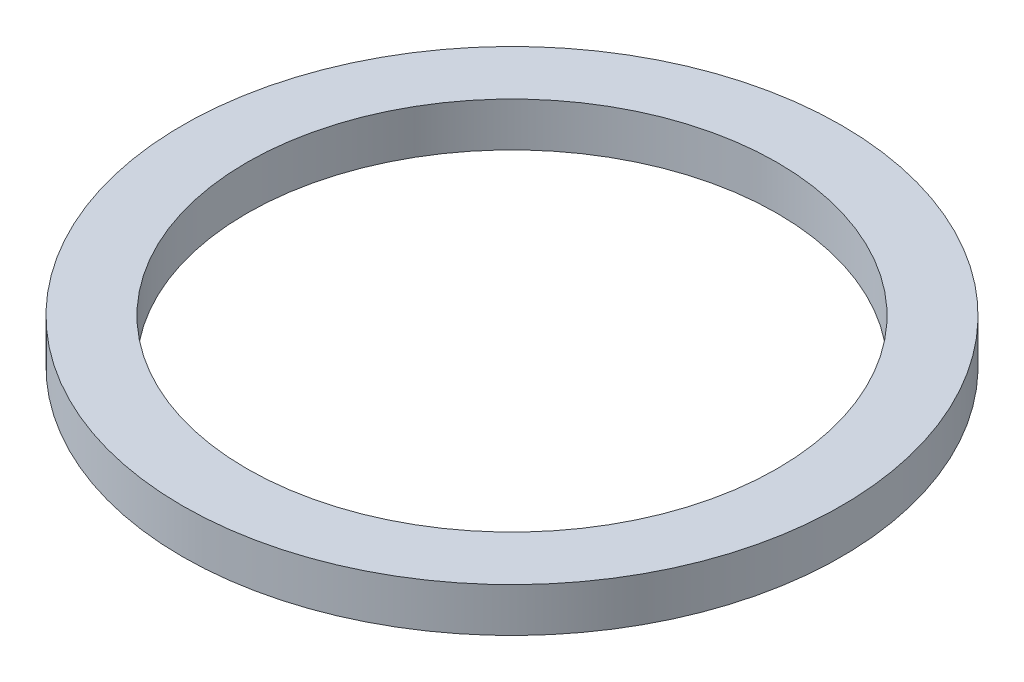
SolidWorks part; units mm, degrees
material "ABS"
ref_plane "Front Plane" through (0, 0, 0) normal (0, 0, 1) x (1, 0, 0)
ref_plane "Top Plane" through (0, 0, 0) normal (0, 1, 0) x (1, 0, 0)
ref_plane "Right Plane" through (0, 0, 0) normal (1, 0, 0) x (0, 0, -1)
sketch "Sketch2" plane through (0, 0, 0) normal (0, 1, 0) x (1, 0, 0)
  circle A0 centre (0, 0) radius 34
  circle A1 centre (0, 0) radius 42.25
  dimension "D1" = 68
  dimension "D2" = 84.5
extrude "Boss-Extrude1" add sketch "Sketch2" along normal blind 5.65
equation "\"L1L\"=500"
equation "\"L1Thick\"=6.35"
equation "\"Harm-Drive-Outer\"=74.5"
equation "\"L1-Spacing\"=110"
equation "\"L-Bracket-HoleToWall\"=12.5"
equation "\"L-Bracket-HoleToSide\"=11"
equation "\"Bracket-Hole-D\"=6.8"
equation "\"D2@Sketch2\"=(\"Harm-Drive-Outer\"/2+5)*2"
